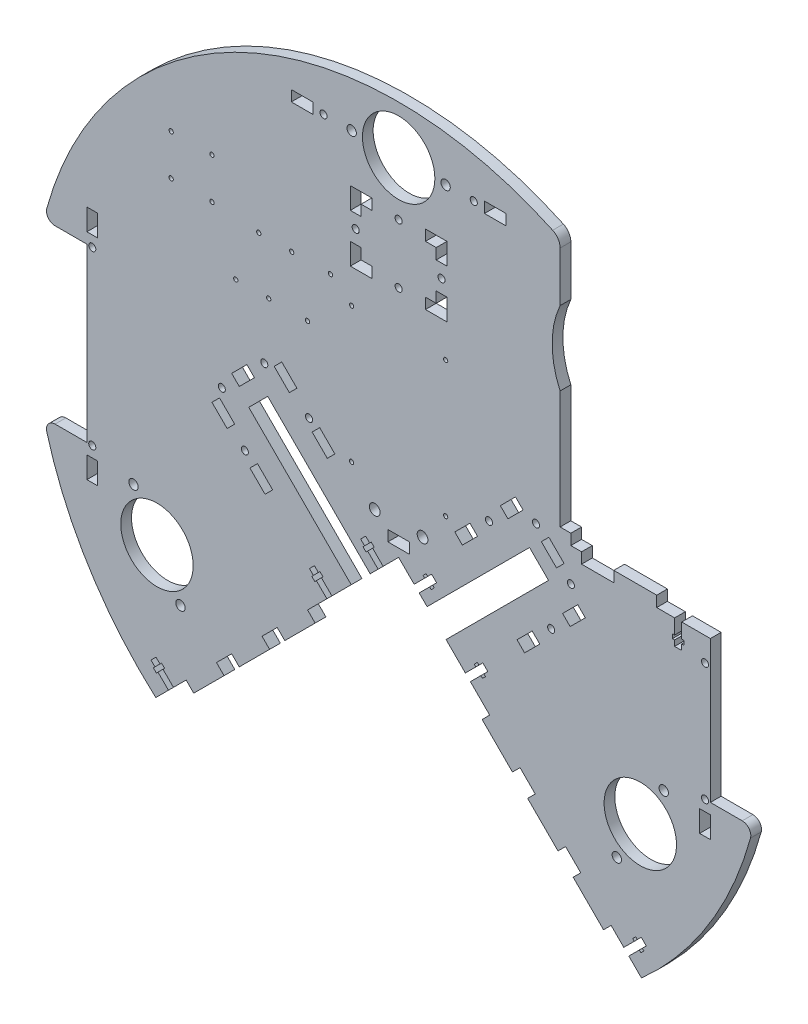
SolidWorks part; units mm, degrees
ref_plane "Front Plane" through (0, 0, 0) normal (0, 0, 1) x (1, 0, 0)
ref_plane "Top Plane" through (0, 0, 0) normal (0, 1, 0) x (1, 0, 0)
ref_plane "Right Plane" through (0, 0, 0) normal (1, 0, 0) x (0, 0, -1)
sketch "Sketch1" plane through (0, 0, 0) normal (0, 0, 1) x (1, 0, 0)
  circle A0 centre (0, 0) radius 215.9
  dimension "D1" = 431.8
extrude "Base Plate Extrusion" add sketch "Sketch1" along normal blind 6.35
sketch "Sketch2" plane through (0, 0, 6.35) normal (0, 0, 1) x (1, 0, 0)
  line L0 (0, 0) -> (0, -230.9791) construction
  line L1 (0, -17.4608) -> (143.6841, -161.1449)
  line L2 (0, -17.4608) -> (-143.6841, -161.1449)
  circle A1 centre (0, 0) radius 215.9 construction
  arc A2 (143.6841, -161.1449) -> (-143.6841, -161.1449) centre (0, 0) cw
  dimension "D1" = 90
  dimension "D2" = 203.2
extrude "V Funnel Cut" cut sketch "Sketch2" against normal through all
sketch "Sketch3" plane through (0, 0, 6.35) normal (0, 0, 1) x (1, 0, 0)
  line L0 (0, 0) -> (251.7982, 0) construction
  line L1 (209.8384, 50.8) -> (184.4384, 50.8)
  line L2 (209.8384, 50.8) -> (209.8384, -50.8)
  line L3 (209.8384, -50.8) -> (184.4384, -50.8)
  line L4 (184.4384, 50.8) -> (184.4384, -50.8)
  arc A0 (143.6841, -161.1449) -> (-143.6841, -161.1449) centre (0, 0) ccw construction
  arc A1 (209.8384, 50.8) -> (209.8384, -50.8) centre (0, 0) cw
  arc M7 (143.6841, -161.1449) -> (-143.6841, -161.1449) centre (0, 0) ccw
  dimension "D1" = 25.4
  dimension "D2" = 101.6
extrude "Wheel Track Cut" cut sketch "Sketch3" against normal through all contours L2 L0 A1 | L4 L0 L2 L1 | L0 L4 L3 L2 | L0 L2 M7 region at (197.1384, 25.4, 6.35) region at (197.1384, -25.4, 6.35) region at (212.266, 19.0862, 6.35) region at (212.266, -19.0862, 6.35)
mirror "Wheel Track Cut Mirror" about plane through (0, 0, 0) normal (1, 0, 0) of "Wheel Track Cut"
sketch "Sketch4" plane through (0, 0, 6.35) normal (0, 0, 1) x (1, 0, 0)
  line L0 (88.68, 15.0926) -> (77.4547, 26.3179)
  line L1 (88.68, 15.0926) -> (28.0633, -45.5241)
  line L2 (77.4547, 26.3179) -> (16.838, -34.2988)
  line L3 (28.0633, -45.5241) -> (16.838, -34.2988)
  line L4 (84.3174, 21.9553) -> (56.956, -5.4061) construction
  line L5 (65.1069, -1.7454) -> (69.5826, 2.7303) construction
  line L6 (65.0924, 7.2204) -> (60.6167, 2.7447) construction
  line L7 (143.6841, -161.1449) -> (0, -17.4608) construction
  dimension "D1" = 15.875
  dimension "D2" = 85.725
extrude "Silo Picker Clearance" cut sketch "Sketch4" against normal through all
sketch "Sketch5" plane through (0, 0, 6.35) normal (0, 0, 1) x (1, 0, 0)
  line L0 (-4.4901, -21.951) -> (0, -17.4608)
  line L1 (-4.4901, -21.951) -> (0, -26.4411)
  line L2 (0, -17.4608) -> (4.4901, -21.951)
  line L3 (0, -26.4411) -> (4.4901, -21.951)
  line L4 (0, -17.4608) -> (-143.6841, -161.1449) construction
  line L6 (4.4901, -21.951) -> (0, -26.4411) construction
  dimension "D1" = 6.35
extrude "V Funnel Corner" add sketch "Sketch5" against normal up to surface (6.35 mm away) up to face at (14.0691, -14.8765, 0)
mirror "Dump Picker Clearance" about plane through (0, 0, 0) normal (1, 0, 0) of "Silo Picker Clearance"
sketch "Sketch6" plane through (8.7304, -8.7304, 0) normal (0.7071, -0.7071, 0) x (0, 0, -1)
  line L0 (-6.35, -52.0342) -> (-6.35, -215.5467) construction
  line L1 (-6.35, -190.1467) -> (0, -190.1467)
  line L2 (-6.35, -190.1467) -> (-6.35, -164.7467)
  line L3 (-6.35, -164.7467) -> (0, -164.7467)
  line L4 (0, -190.1467) -> (0, -164.7467)
  line L5 (0, -52.0342) -> (0, -215.5467) construction
  dimension "D1" = 25.4
  dimension "D2" = 25.4
extrude "V Funnel Tab Left" add sketch "Sketch6" along normal blind 6.35
pattern_linear "V Funnel Tab Pattern Left" count 3 spacing 38.1 along (0.7071, 0.7071, 0) of "V Funnel Tab Left"
sketch "Sketch7" plane through (-8.7304, -8.7304, 0) normal (-0.7071, -0.7071, 0) x (0, 0, 1)
  line L0 (6.35, -215.5467) -> (6.35, -52.0342) construction
  line L1 (6.35, -164.7467) -> (0, -164.7467)
  line L2 (6.35, -164.7467) -> (6.35, -190.1467)
  line L3 (6.35, -190.1467) -> (0, -190.1467)
  line L4 (0, -164.7467) -> (0, -190.1467)
  line L5 (0, -215.5467) -> (0, -52.0342) construction
  dimension "D1" = 25.4
  dimension "D2" = 25.4
extrude "V Funnel Tab Right" add sketch "Sketch7" along normal blind 6.35
pattern_linear "V Funnel Tab Pattern Right" count 3 spacing 38.1 along (-0.7071, 0.7071, 0) of "V Funnel Tab Right"
sketch "Sketch8" plane through (0, 0, 0) normal (0, 0, -1) x (-1, 0, 0)
  line L0 (-70.046, -24.645) -> (-79.0263, -15.6648)
  line L1 (-79.0263, -15.6648) -> (-83.5164, -20.1549)
  line L2 (-83.5164, -20.1549) -> (-74.5361, -29.1352)
  line L3 (-74.5361, -29.1352) -> (-70.046, -24.645)
  line L4 (-96.9868, 2.2957) -> (-101.4769, -2.1944)
  line L5 (-101.4769, -2.1944) -> (-110.4572, 6.7859)
  line L6 (-110.4572, 6.7859) -> (-105.967, 11.276)
  line L7 (-105.967, 11.276) -> (-96.9868, 2.2957)
  line L8 (-97.8965, 28.3267) -> (-88.9163, 37.307)
  line L9 (-88.9163, 37.307) -> (-84.4262, 32.8169)
  line L10 (-84.4262, 32.8169) -> (-93.4064, 23.8366)
  line L11 (-93.4064, 23.8366) -> (-97.8965, 28.3267)
  line L12 (-64.6578, 34.6246) -> (-60.1677, 39.1148)
  line L13 (-60.1677, 39.1148) -> (-69.148, 48.095)
  line L14 (-69.148, 48.095) -> (-73.6381, 43.6049)
  line L15 (-73.6381, 43.6049) -> (-64.6578, 34.6246)
  line L16 (-46.6973, 16.6641) -> (-42.2072, 21.1543)
  line L17 (-42.2072, 21.1543) -> (-33.2269, 12.174)
  line L18 (-33.2269, 12.174) -> (-37.7171, 7.6839)
  line L19 (-37.7171, 7.6839) -> (-46.6973, 16.6641)
  line L20 (-105.967, 11.276) -> (-110.4572, 6.7859) construction
  line L21 (-69.148, 48.095) -> (-73.6381, 43.6049) construction
extrude "Silo Arm Tab Holes" cut sketch "Sketch8" against normal blind 6.35
sketch "Sketch10" plane through (0, 0, 0) normal (0, 0, -1) x (-1, 0, 0)
  line L0 (51.1875, 21.1543) -> (42.2072, 12.174)
  line L1 (42.2072, 12.174) -> (37.7171, 16.6641)
  line L2 (37.7171, 16.6641) -> (46.6973, 25.6444)
  line L3 (46.6973, 25.6444) -> (51.1875, 21.1543)
  line L4 (64.6578, 34.6246) -> (60.1677, 39.1148)
  line L5 (60.1677, 39.1148) -> (69.148, 48.095)
  line L6 (69.148, 48.095) -> (73.6381, 43.6049)
  line L7 (73.6381, 43.6049) -> (64.6578, 34.6246)
  line L8 (89.8026, 36.4207) -> (85.3124, 31.9306)
  line L9 (85.3124, 31.9306) -> (94.2927, 22.9503)
  line L10 (94.2927, 22.9503) -> (98.7828, 27.4404)
  line L11 (98.7828, 27.4404) -> (89.8026, 36.4207)
  line L12 (105.967, 11.276) -> (96.9868, 2.2957)
  line L13 (96.9868, 2.2957) -> (101.4769, -2.1944)
  line L14 (101.4769, -2.1944) -> (110.4572, 6.7859)
  line L15 (110.4572, 6.7859) -> (105.967, 11.276)
  line L16 (88.0065, -15.6648) -> (83.5164, -11.1747)
  line L17 (83.5164, -11.1747) -> (74.5361, -20.1549)
  line L18 (74.5361, -20.1549) -> (79.0263, -24.645)
  line L19 (79.0263, -24.645) -> (88.0065, -15.6648)
  line L20 (37.7171, 16.6641) -> (42.2072, 12.174) construction
  line L21 (74.5361, -20.1549) -> (79.0263, -24.645) construction
extrude "Dump Arm Tab Holes" cut sketch "Sketch10" against normal blind 6.35
sketch "Sketch11" plane through (0, 0, 0) normal (0, 0, -1) x (-1, 0, 0)
  line L1 (184.4384, -69.85) -> (178.0884, -69.85)
  line L2 (184.4384, -69.85) -> (184.4384, -57.15)
  line L3 (184.4384, -57.15) -> (178.0884, -57.15)
  line L4 (178.0884, -69.85) -> (178.0884, -57.15)
  line L5 (184.4384, 57.15) -> (178.0884, 57.15)
  line L6 (184.4384, 57.15) -> (184.4384, 69.85)
  line L7 (184.4384, 69.85) -> (178.0884, 69.85)
  line L8 (178.0884, 57.15) -> (178.0884, 69.85)
  line L9 (-178.0884, -69.85) -> (-184.4384, -69.85)
  line L10 (-178.0884, -69.85) -> (-178.0884, -57.15)
  line L11 (-178.0884, -57.15) -> (-184.4384, -57.15)
  line L12 (-184.4384, -69.85) -> (-184.4384, -57.15)
  line L13 (-178.0884, 57.15) -> (-184.4384, 57.15)
  line L14 (-178.0884, 57.15) -> (-178.0884, 69.85)
  line L15 (-178.0884, 69.85) -> (-184.4384, 69.85)
  line L16 (-184.4384, 57.15) -> (-184.4384, 69.85)
extrude "Wheel Support Tab Holes" cut sketch "Sketch11" against normal blind 6.35
sketch "Sketch13" plane through (0, 0, 6.35) normal (0, 0, 1) x (1, 0, 0)
  circle A0 centre (0, 187.325) radius 21.4313
  circle A1 centre (27.7812, 187.325) radius 2.7781
  circle A2 centre (-27.7813, 187.325) radius 2.7781
  dimension "D1" = 42.8625
  dimension "D2" = 5.5562
extrude "Caster Wheel Hole" cut sketch "Sketch13" against normal through all
sketch "Sketch14" plane through (0, 0, 6.35) normal (0, 0, 1) x (1, 0, 0)
  line L0 (184.4384, 48.6664) -> (178.0884, 52.9336) construction
  line L1 (184.4384, 50.8) -> (184.4384, -50.8) construction
  line L2 (178.0884, 48.6664) -> (184.4384, 48.6664) construction
  line L3 (184.4384, 52.9336) -> (178.0884, 48.6664) construction
  line L4 (184.4384, -52.9336) -> (178.0884, -48.6664) construction
  line L5 (184.4384, -48.6664) -> (178.0884, -52.9336) construction
  line L6 (178.0884, -48.6664) -> (184.4384, -48.6664) construction
  circle A0 centre (181.2634, 50.8) radius 2.0955
  circle A1 centre (181.2634, -50.8) radius 2.0955
  dimension "D1" = 4.191
extrude "Wheel Support Hole" cut sketch "Sketch14" against normal through all
mirror "Wheel Support Hole Mirror" about plane through (0, 0, 0) normal (1, 0, 0) of "Wheel Support Hole"
sketch "Sketch15" plane through (0, 0, 6.35) normal (0, 0, 1) x (1, 0, 0)
  line L0 (-134.7038, -152.1647) -> (-152.6084, -134.2601) construction
  line L1 (-125.7236, -143.1844) -> (-143.6841, -161.1449) construction
  line L2 (-40.9724, -58.4333) -> (-60.7132, -38.6924) construction
  line L3 (-28.0633, -45.5241) -> (-53.8815, -71.3424) construction
  line L4 (-10.6641, -28.1249) -> (-27.2834, -11.5055) construction
  line L5 (-4.4901, -21.951) -> (-16.838, -34.2988) construction
  line B0 (-136.1856, -153.6464) -> (-133.2221, -150.6829)
  line B1 (-141.2145, -142.6905) -> (-140.2716, -141.7476)
  line B2 (-140.2716, -141.7476) -> (-138.4755, -143.5436)
  line B3 (-138.4755, -143.5436) -> (-139.4185, -144.4866)
  line B4 (-139.4185, -144.4866) -> (-133.2221, -150.6829)
  line B5 (-141.2145, -142.6905) -> (-143.5494, -140.3556)
  line B6 (-143.5494, -140.3556) -> (-146.5129, -143.3191)
  line B7 (-144.178, -145.654) -> (-146.5129, -143.3191)
  line B8 (-142.382, -147.45) -> (-136.1856, -153.6464)
  line B9 (-143.3249, -148.393) -> (-142.382, -147.45)
  line B10 (-145.1209, -146.5969) -> (-143.3249, -148.393)
  line B11 (-144.178, -145.654) -> (-145.1209, -146.5969)
  line B12 (-42.4542, -59.915) -> (-39.4907, -56.9515)
  line B13 (-47.4831, -48.9591) -> (-46.5402, -48.0162)
  line B14 (-46.5402, -48.0162) -> (-44.7441, -49.8122)
  line B15 (-44.7441, -49.8122) -> (-45.6871, -50.7551)
  line B16 (-45.6871, -50.7551) -> (-39.4907, -56.9515)
  line B17 (-47.4831, -48.9591) -> (-49.818, -46.6242)
  line B18 (-49.818, -46.6242) -> (-52.7815, -49.5877)
  line B19 (-50.4466, -51.9226) -> (-52.7815, -49.5877)
  line B20 (-48.6505, -53.7186) -> (-42.4542, -59.915)
  line B21 (-49.5935, -54.6615) -> (-48.6505, -53.7186)
  line B22 (-51.3895, -52.8655) -> (-49.5935, -54.6615)
  line B23 (-50.4466, -51.9226) -> (-51.3895, -52.8655)
  line B24 (-12.1458, -29.6066) -> (-9.1823, -26.6431)
  line B25 (-17.1747, -18.6507) -> (-16.2318, -17.7078)
  line B26 (-16.2318, -17.7078) -> (-14.4358, -19.5038)
  line B27 (-14.4358, -19.5038) -> (-15.3787, -20.4468)
  line B28 (-15.3787, -20.4468) -> (-9.1823, -26.6431)
  line B29 (-17.1747, -18.6507) -> (-19.5096, -16.3159)
  line B30 (-19.5096, -16.3159) -> (-22.4731, -19.2793)
  line B31 (-20.1382, -21.6142) -> (-22.4731, -19.2793)
  line B32 (-18.3422, -23.4103) -> (-12.1458, -29.6066)
  line B33 (-19.2851, -24.3532) -> (-18.3422, -23.4103)
  line B34 (-21.0812, -22.5571) -> (-19.2851, -24.3532)
  line B35 (-20.1382, -21.6142) -> (-21.0812, -22.5571)
sketch_block_instance "TSlot-1"
sketch_block "TSlot" parameters "D1"=3.302, "D2"=2.54, "D3"=3.175, "D4"=8.763, "D5"=1.3462
sketch_block_instance "TSlot-3"
sketch_block_instance "TSlot-4"
extrude "V Funnel T Slot Cut Out" cut sketch "Sketch15" against normal through all
mirror "V Funnel T Slot Cut Out Mirror" about plane through (0, 0, 0) normal (1, 0, 0) of "V Funnel T Slot Cut Out"
sketch "Sketch19" plane through (0, 0, 6.35) normal (0, 0, 1) x (1, 0, 0)
  line L0 (46.5836, 190.5) -> (42.3164, 184.15) construction
  line L1 (46.5836, 184.15) -> (42.3164, 190.5) construction
  line L2 (-42.3164, 190.5) -> (-46.5836, 184.15) construction
  line L3 (-42.3164, 184.15) -> (-46.5836, 190.5) construction
  circle A0 centre (44.45, 187.325) radius 2.0955
  circle A1 centre (-44.45, 187.325) radius 2.0955
  dimension "D1" = 4.191
extrude "Switch Plate Holes" cut sketch "Sketch19" against normal through all
sketch "Sketch20" plane through (0, 0, 0) normal (0, 0, -1) x (-1, 0, 0)
  line L1 (-50.8, 184.15) -> (-63.5, 184.15)
  line L2 (-50.8, 184.15) -> (-50.8, 190.5)
  line L3 (-50.8, 190.5) -> (-63.5, 190.5)
  line L4 (-63.5, 184.15) -> (-63.5, 190.5)
  line L5 (63.5, 184.15) -> (50.8, 184.15)
  line L6 (63.5, 184.15) -> (63.5, 190.5)
  line L7 (63.5, 190.5) -> (50.8, 190.5)
  line L8 (50.8, 184.15) -> (50.8, 190.5)
extrude "Swith Plate Tab Holes" cut sketch "Sketch20" against normal through all
sketch "Sketch26" plane through (0, 0, 6.35) normal (0, 0, 1) x (1, 0, 0)
  line L0 (89.5152, -5.1758) -> (90.988, -12.6833) construction
  line L1 (86.4978, -8.1932) -> (94.0053, -9.666) construction
  line L2 (52.6961, 31.6432) -> (54.1689, 24.1357) construction
  line L3 (49.6788, 28.6258) -> (57.1863, 27.1531) construction
  line L4 (105.6855, 20.5377) -> (98.178, 19.065) construction
  line L5 (102.6682, 23.5551) -> (101.1954, 16.0476) construction
  line L6 (82.0136, 44.2097) -> (80.5408, 36.7022) construction
  line L7 (85.0309, 41.1923) -> (77.5234, 39.7196) construction
  circle A0 centre (90.2516, -8.9296) radius 2.0955
  circle A1 centre (53.4325, 27.8895) radius 2.0955
  circle A2 centre (101.9318, 19.8014) radius 2.0955
  circle A3 centre (81.2772, 40.4559) radius 2.0955
  dimension "D1" = 4.191
extrude "Silo Arm Holes" cut sketch "Sketch26" against normal through all
sketch "Sketch27" plane through (0, 0, 6.35) normal (0, 0, 1) x (1, 0, 0)
  line L0 (-49.2298, 28.1768) -> (-56.7373, 26.7041) construction
  line L1 (-52.2471, 31.1942) -> (-53.7199, 23.6867) construction
  line L2 (-80.2116, 46.0116) -> (-78.7389, 38.5041) construction
  line L3 (-83.229, 42.9942) -> (-75.7215, 41.5215) construction
  line L4 (-105.3564, 20.8669) -> (-103.8836, 13.3594) construction
  line L5 (-108.3737, 17.8495) -> (-100.8662, 16.3768) construction
  line L6 (-94.6968, -8.9745) -> (-87.2432, -7.4479) construction
  line L7 (-91.7333, -11.938) -> (-90.2067, -4.4844) construction
  circle A0 centre (-52.9835, 27.4404) radius 2.0955
  circle A1 centre (-79.4753, 42.2579) radius 2.0955
  circle A2 centre (-104.62, 17.1131) radius 2.0955
  circle A3 centre (-90.97, -8.2112) radius 2.0955
  dimension "D1" = 4.191
extrude "Dump Arm Holes" cut sketch "Sketch27" against normal through all
fillet "Wheel Slot Fillet" radius 5.08 4 edges at (209.8384, -50.8, 3.175) (209.8384, 50.8, 3.175) (-209.8384, -50.8, 3.175) (-209.8384, 50.8, 3.175)
sketch "Sketch28" plane through (0, 0, 6.35) normal (0, 0, 1) x (1, 0, 0)
  line L0 (0, 0) -> (0, 258.9974) construction
  line L1 (0, 0) -> (249.4479, -144.0188) construction
  line L2 (0, 0) -> (-249.719, -144.1753) construction
  line L3 (-142.9808, -82.55) -> (-156.8714, -58.4907) construction
  line L4 (-27.7813, 187.325) -> (0, 187.325) construction
  line L5 (-142.9808, -82.55) -> (-129.0902, -106.6093) construction
  circle A0 centre (-142.9808, -82.55) radius 21.4313
  circle A1 centre (0, 187.325) radius 21.4313 construction
  circle A2 centre (-156.8714, -58.4907) radius 2.7781
  circle A3 centre (-27.7813, 187.325) radius 2.7781 construction
  circle A4 centre (-129.0902, -106.6093) radius 2.7781
  dimension "D1" = 120
  dimension "D2" = 120
  dimension "D3" = 165.1
extrude "Front Caster Holes" cut sketch "Sketch28" against normal through all
mirror "Front Caster Hole Mirror" about plane through (0, 0, 0) normal (1, 0, 0) of "Front Caster Holes"
sketch "Gyro Holes" plane through (0, 0, 6.35) normal (0, 0, 1) x (1, 0, 0)
  line L1 (-134.5682, 109.4626) -> (-110.4382, 109.4626) construction
  line L2 (-134.5682, 109.4626) -> (-134.5682, 133.5926) construction
  line L3 (-134.5682, 133.5926) -> (-110.4382, 133.5926) construction
  line L4 (-110.4382, 109.4626) -> (-110.4382, 133.5926) construction
  line L5 (-134.5682, 109.4626) -> (-110.4382, 133.5926) construction
  line L6 (-134.5682, 133.5926) -> (-110.4382, 109.4626) construction
  circle A0 centre (-134.5682, 133.5926) radius 1.27
  circle A1 centre (-110.4382, 133.5926) radius 1.27
  circle A2 centre (-110.4382, 109.4626) radius 1.27
  circle A3 centre (-134.5682, 109.4626) radius 1.27
  point P0 (-122.5032, 121.5276)
  dimension "D2" = 24.13
  dimension "D1" = 2.54
extrude "GyroHoles" cut sketch "Gyro Holes" against normal through all
sketch "MotorControllerHoleSketch" plane through (0, 0, 6.35) normal (0, 0, 1) x (1, 0, 0)
  line L0 (0, 215.9) -> (0, -26.4411) construction
  line L2 (-27.82, 17.5746) -> (27.82, 17.5746) construction
  line L3 (-27.82, 17.5746) -> (-27.82, 97.6146) construction
  line L4 (-27.82, 97.6146) -> (27.82, 97.6146) construction
  line L5 (27.82, 17.5746) -> (27.82, 97.6146) construction
  line L6 (-27.82, 17.5746) -> (27.82, 97.6146) construction
  line L7 (-27.82, 97.6146) -> (27.82, 17.5746) construction
  arc A0 (208.1777, 57.2265) -> (-208.1777, 57.2265) centre (0, 0) ccw construction
  circle A1 centre (-27.82, 97.6146) radius 1.25
  circle A2 centre (27.82, 97.6146) radius 1.25
  circle A3 centre (27.82, 17.5746) radius 1.25
  circle A4 centre (-27.82, 17.5746) radius 1.25
  point P6 (0, 57.5946)
  dimension "D1" = 2.5
  dimension "D2" = 55.64
  dimension "D3" = 80.04
extrude "Motor Controller Hole" cut sketch "MotorControllerHoleSketch" against normal through all
sketch "Sketch31" plane through (0, 0, 6.35) normal (0, 0, 1) x (1, 0, 0)
  line L0 (-58.5988, 118.6025) -> (-58.5988, 61.2016) construction
  line L1 (-40.3087, 76.7541) -> (-53.9191, 76.7541) construction
  line L2 (-40.3087, 76.7541) -> (-40.3087, 107.5065) construction
  line L3 (-40.3087, 107.5065) -> (-53.9191, 107.5065) construction
  line L4 (-53.9191, 76.7541) -> (-53.9191, 107.5065) construction
  line L5 (-40.3087, 76.7541) -> (-53.9191, 107.5065) construction
  line L6 (-40.3087, 107.5065) -> (-53.9191, 76.7541) construction
  line L7 (-63.2785, 76.7541) -> (-76.8888, 76.7541) construction
  line L8 (-63.2785, 76.7541) -> (-63.2785, 107.5065) construction
  line L9 (-63.2785, 107.5065) -> (-76.8888, 107.5065) construction
  line L10 (-76.8888, 76.7541) -> (-76.8888, 107.5065) construction
  line L11 (-63.2785, 76.7541) -> (-76.8888, 107.5065) construction
  line L12 (-63.2785, 107.5065) -> (-76.8888, 76.7541) construction
  line L13 (-70.0836, 92.1303) -> (-47.1139, 92.1303) construction
  line L15 (-82.7354, 76.7541) -> (-96.3457, 76.7541) construction
  line L16 (-82.7354, 76.7541) -> (-82.7354, 107.5065) construction
  line L17 (-82.7354, 107.5065) -> (-96.3457, 107.5065) construction
  line L18 (-96.3457, 76.7541) -> (-96.3457, 107.5065) construction
  line L19 (-82.7354, 76.7541) -> (-96.3457, 107.5065) construction
  line L20 (-82.7354, 107.5065) -> (-96.3457, 76.7541) construction
  circle A0 centre (-76.8888, 76.7541) radius 1.27
  circle A1 centre (-63.2785, 107.5065) radius 1.27
  circle A2 centre (-53.9191, 76.7541) radius 1.27
  circle A3 centre (-40.3087, 107.5065) radius 1.27
  circle A4 centre (-82.7354, 107.5065) radius 1.27
  circle A5 centre (-96.3457, 76.7541) radius 1.27
  point P0 (-47.1139, 92.1303)
  point P5 (-70.0836, 92.1303)
  point P18 (-89.5406, 92.1303)
  dimension "D1" = 2.54
  dimension "D2" = 33.6296
extrude "BuckConverterHoles" cut sketch "Sketch31" against normal through all
sketch "Sketch34" plane through (0, 0, 0) normal (0, 0, -1) x (-1, 0, 0)
  line L1 (-28.575, 158.75) -> (-15.875, 158.75)
  line L2 (-28.575, 158.75) -> (-28.575, 152.4)
  line L3 (-22.225, 152.4) -> (-15.875, 152.4)
  line L4 (-15.875, 158.75) -> (-15.875, 152.4)
  line L5 (15.875, 158.75) -> (28.575, 158.75)
  line L6 (15.875, 158.75) -> (15.875, 152.4)
  line L7 (15.875, 152.4) -> (22.225, 152.4)
  line L8 (28.575, 158.75) -> (28.575, 152.4)
  line L9 (15.875, 123.825) -> (22.225, 123.825)
  line L10 (15.875, 123.825) -> (15.875, 117.475)
  line L11 (15.875, 117.475) -> (28.575, 117.475)
  line L12 (28.575, 123.825) -> (28.575, 117.475)
  line L13 (-22.225, 123.825) -> (-15.875, 123.825)
  line L14 (-28.575, 123.825) -> (-28.575, 117.475)
  line L15 (-28.575, 117.475) -> (-15.875, 117.475)
  line L16 (-15.875, 123.825) -> (-15.875, 117.475)
  line L17 (-28.575, 130.175) -> (-22.225, 130.175)
  line L18 (-28.575, 130.175) -> (-28.575, 123.825)
  line L20 (-22.225, 130.175) -> (-22.225, 123.825)
  line L22 (-28.575, 152.4) -> (-28.575, 146.05)
  line L23 (-28.575, 146.05) -> (-22.225, 146.05)
  line L24 (-22.225, 152.4) -> (-22.225, 146.05)
  line L26 (22.225, 152.4) -> (22.225, 146.05)
  line L27 (22.225, 146.05) -> (28.575, 146.05)
  line L28 (28.575, 152.4) -> (28.575, 146.05)
  line L29 (22.225, 130.175) -> (28.575, 130.175)
  line L30 (22.225, 130.175) -> (22.225, 123.825)
  line L32 (28.575, 130.175) -> (28.575, 123.825)
extrude "Cut-Extrude6" cut sketch "Sketch34" against normal through all
sketch "Sketch35" plane through (0, 0, 6.35) normal (0, 0, 1) x (1, 0, 0)
  line L0 (-22.225, 136.017) -> (-28.575, 140.208) construction
  line L1 (-28.575, 136.017) -> (-22.225, 140.208) construction
  line L2 (-2.0955, 152.4) -> (2.0955, 158.75) construction
  line L3 (2.0955, 152.4) -> (-2.0955, 158.75) construction
  line L4 (22.225, 136.017) -> (28.575, 140.208) construction
  line L5 (22.225, 140.208) -> (28.575, 136.017) construction
  line L6 (2.0955, 123.825) -> (-2.0955, 117.475) construction
  line L7 (-2.0955, 123.825) -> (2.0955, 117.475) construction
  circle A0 centre (0, 120.65) radius 2.0955
  circle A1 centre (25.4, 138.1125) radius 2.0955
  circle A2 centre (0, 155.575) radius 2.0955
  circle A3 centre (-25.4, 138.1125) radius 2.0955
  dimension "D1" = 4.191
extrude "Cut-Extrude7" cut sketch "Sketch35" against normal through all
sketch "Sketch37" [suppressed] plane through (0, 0, 0) normal (0, 0, -1) x (-1, 0, 0)
  line L0 (-86.0134, 49.1901) -> (-174.9134, 49.1901) construction
  line L1 (-117.7634, 49.1901) -> (-143.1634, 49.1901)
  line L2 (-117.7634, 49.1901) -> (-117.7634, 55.5401)
  line L3 (-117.7634, 55.5401) -> (-143.1634, 55.5401)
  line L4 (-143.1634, 49.1901) -> (-143.1634, 55.5401)
  line L5 (-117.7634, 49.1901) -> (-117.7634, 55.5401) construction
sketch "Sketch41" plane through (0, 0, 6.35) normal (0, 0, 1) x (1, 0, 0)
  line L0 (95.5384, 193.611) -> (95.5384, 45.8763)
  line L1 (95.5384, 49.1901) -> (95.5384, 45.8763) construction
  line L2 (95.5384, 45.8763) -> (101.8884, 45.8763)
  line L3 (101.8884, 45.8763) -> (101.8884, 39.5263)
  line L4 (101.8884, 39.5263) -> (108.2384, 39.5263)
  line L5 (108.2384, 39.5263) -> (108.2384, 33.1763)
  line L6 (108.2384, 33.1763) -> (218.8605, 33.1763)
  line L7 (218.8605, 33.1763) -> (218.8605, 193.611)
  line L8 (218.8605, 193.611) -> (95.5384, 193.611)
  arc A0 (208.1777, 57.2265) -> (-208.1777, 57.2265) centre (0, 0) ccw construction
extrude "Cut-Extrude13" cut sketch "Sketch41" against normal through all
fillet "Fillet1" radius 7.62 1 edges at (95.5384, 193.611, 3.175)
sketch "Sketch42" plane through (0, 0, 6.35) normal (0, 0, 1) x (1, 0, 0)
  line L0 (95.5384, 159.3081) -> (95.5384, 115.5739)
  line L1 (95.5384, 188.8145) -> (95.5384, 45.8763) construction
  arc A1 (95.5384, 115.5739) -> (95.5384, 159.3081) centre (143.7787, 137.441) cw
extrude "Cut-Extrude14" cut sketch "Sketch42" against normal through all
sketch "Sketch44" plane through (0, 33.1763, 0) normal (0, 1, 0) x (1, 0, 0)
  line L0 (108.2384, -6.35) -> (184.4384, -6.35) construction
  line L1 (127.2884, -6.35) -> (152.6884, -6.35)
  line L2 (127.2884, -6.35) -> (127.2884, 0)
  line L3 (127.2884, 0) -> (152.6884, 0)
  line L4 (152.6884, -6.35) -> (152.6884, 0)
  line L5 (108.2384, 0) -> (184.4384, 0) construction
extrude "Boss-Extrude2" add sketch "Sketch44" along normal blind 6.35
sketch "Sketch45" plane through (0, 0, 6.35) normal (0, 0, 1) x (1, 0, 0)
  line L0 (152.6884, 33.1763) -> (184.4384, 33.1763) construction
  line L1 (163.2929, 39.5263) -> (163.2929, 33.1763) construction
  line B0 (167.4839, 33.1763) -> (163.2929, 33.1763)
  line B1 (163.2929, 21.8733) -> (161.9594, 21.8733)
  line B2 (161.9594, 21.8733) -> (161.9594, 24.4133)
  line B3 (161.9594, 24.4133) -> (163.2929, 24.4133)
  line B4 (163.2929, 24.4133) -> (163.2929, 33.1763)
  line B5 (163.2929, 21.8733) -> (163.2929, 18.5713)
  line B6 (163.2929, 18.5713) -> (167.4839, 18.5713)
  line B7 (167.4839, 21.8733) -> (167.4839, 18.5713)
  line B8 (167.4839, 24.4133) -> (167.4839, 33.1763)
  line B9 (168.8174, 24.4133) -> (167.4839, 24.4133)
  line B10 (168.8174, 21.8733) -> (168.8174, 24.4133)
  line B11 (167.4839, 21.8733) -> (168.8174, 21.8733)
  line B12 (165.3884, 33.1763) -> (165.3884, 18.5713) construction
  line B13 (161.9594, 23.1433) -> (172.0532, 23.1433) construction
sketch_block_instance "TSlot-7"
extrude "Cut-Extrude15" cut sketch "Sketch45" against normal through all
sketch "Sketch47" plane through (0, 0, 0) normal (0, 0, -1) x (-1, 0, 0)
  line L1 (-6.35, -12.6983) -> (6.35, -12.6983)
  line L2 (-6.35, -12.6983) -> (-6.35, -6.3483)
  line L3 (-6.35, -6.3483) -> (6.35, -6.3483)
  line L4 (6.35, -12.6983) -> (6.35, -6.3483)
extrude "Cut-Extrude16" cut sketch "Sketch47" against normal through all
extrude "Boss-Extrude1" [suppressed] add sketch "Sketch37" against normal up to surface (6.35 mm away)
sketch "Sketch38" plane through (0, 0, 0) normal (0, 0, -1) x (-1, 0, 0)
  line L2 (-186.392, 104.3946) -> (-275.292, 104.3946) construction
  line L4 (-143.1634, 55.5401) -> (-143.1634, 49.1901) construction
  line L5 (-268.942, 186.9446) -> (-268.942, 110.7446) construction
  line L7 (-192.742, 110.7446) -> (-192.742, 186.9446) construction
  line L8 (-117.7634, 49.1901) -> (-117.7634, 55.5401) construction
  line B0 (-153.1572, 104.3946) -> (-157.3482, 104.3946)
  line B1 (-157.3482, 93.0916) -> (-158.6817, 93.0916)
  line B2 (-158.6817, 93.0916) -> (-158.6817, 95.6316)
  line B3 (-158.6817, 95.6316) -> (-157.3482, 95.6316)
  line B4 (-157.3482, 95.6316) -> (-157.3482, 104.3946)
  line B5 (-157.3482, 93.0916) -> (-157.3482, 89.7896)
  line B6 (-157.3482, 89.7896) -> (-153.1572, 89.7896)
  line B7 (-153.1572, 93.0916) -> (-153.1572, 89.7896)
  line B8 (-153.1572, 95.6316) -> (-153.1572, 104.3946)
  line B9 (-151.8237, 95.6316) -> (-153.1572, 95.6316)
  line B10 (-151.8237, 93.0916) -> (-151.8237, 95.6316)
  line B11 (-153.1572, 93.0916) -> (-151.8237, 93.0916)
  line B12 (-155.2527, 104.3946) -> (-155.2527, 89.7896) construction
  line B13 (-203.9572, 104.3946) -> (-208.1482, 104.3946)
  line B14 (-208.1482, 93.0916) -> (-209.4817, 93.0916)
  line B15 (-209.4817, 93.0916) -> (-209.4817, 95.6316)
  line B16 (-209.4817, 95.6316) -> (-208.1482, 95.6316)
  line B17 (-208.1482, 95.6316) -> (-208.1482, 104.3946)
  line B18 (-208.1482, 93.0916) -> (-208.1482, 89.7896)
  line B19 (-208.1482, 89.7896) -> (-203.9572, 89.7896)
  line B20 (-203.9572, 93.0916) -> (-203.9572, 89.7896)
  line B21 (-203.9572, 95.6316) -> (-203.9572, 104.3946)
  line B22 (-202.6237, 95.6316) -> (-203.9572, 95.6316)
  line B23 (-202.6237, 93.0916) -> (-202.6237, 95.6316)
  line B24 (-203.9572, 93.0916) -> (-202.6237, 93.0916)
  line B25 (-206.0527, 104.3946) -> (-206.0527, 89.7896) construction
sketch_block_instance "TSlot-5"
sketch_block_instance "TSlot-6"
extrude "Cut-Extrude9" [suppressed] cut sketch "Sketch38" against normal through all
sketch "Sketch39" plane through (0, 0, 0) normal (0, 0, -1) x (-1, 0, 0)
  line L0 (-184.4384, 33.1763) -> (-227.6876, 33.1763)
  line L1 (-95.5384, 33.1763) -> (-184.4384, 33.1763)
  line L2 (-95.5384, 33.1763) -> (-95.5384, 122.0763)
  line L3 (-95.5384, 122.0763) -> (-184.4384, 122.0763)
  arc A0 (-227.6876, 33.1763) -> (-184.4384, 122.0763) centre (-22.9914, -11.4365) cw
extrude "Cut-Extrude11" cut sketch "Sketch39" against normal through all
sketch "Sketch40" plane through (0, 0, 6.35) normal (0, 0, 1) x (1, 0, 0)
  line L0 (178.0884, 21.1455) -> (184.4384, 16.9545) construction
  line L1 (184.4384, 33.1763) -> (184.4384, -50.8) construction
  line L2 (178.0884, 16.9545) -> (184.4384, 16.9545) construction
  line L3 (178.0884, 16.9545) -> (184.4384, 21.1455) construction
  circle A0 centre (181.2634, 19.05) radius 2.0955
  dimension "D1" = 4.191
extrude "Cut-Extrude12" cut sketch "Sketch40" against normal through all
sketch "Sketch48" plane through (0, 33.1763, 0) normal (0, 1, 0) x (1, 0, 0)
  line L0 (95.5384, 0) -> (163.2929, 0) construction
  line L1 (95.5384, -6.35) -> (108.2384, -6.35)
  line L2 (95.5384, -6.35) -> (95.5384, 0)
  line L3 (95.5384, 0) -> (108.2384, 0)
  line L4 (108.2384, -6.35) -> (108.2384, 0)
extrude "Boss-Extrude3" add sketch "Sketch48" along normal blind 6.35
sketch "Sketch49" plane through (95.5384, 0, 0) normal (1, 0, 0) x (0, 0, -1)
  line L0 (0, 115.5739) -> (0, 39.5263) construction
  line L1 (-6.35, 39.5263) -> (0, 39.5263)
  line L2 (-6.35, 39.5263) -> (-6.35, 45.8763)
  line L3 (-6.35, 45.8763) -> (0, 45.8763)
  line L4 (0, 39.5263) -> (0, 45.8763)
  line L5 (0, 45.8763) -> (-6.35, 45.8763) construction
extrude "Boss-Extrude4" add sketch "Sketch49" along normal blind 6.35
sketch "Sketch50" plane through (0, 0, 0) normal (0, 0, -1) x (-1, 0, 0)
  line L0 (0, -17.4608) -> (-4.4901, -21.951)
  line L1 (-4.4901, -21.951) -> (0, -26.4411)
  line L2 (0, -26.4411) -> (4.4901, -21.951)
  line L3 (4.4901, -21.951) -> (0, -17.4608)
extrude "Cut-Extrude17" cut sketch "Sketch50" against normal through all
sketch "Sketch51" plane through (0, 0, 0) normal (0, 0, -1) x (-1, 0, 0)
  line L0 (0, 0) -> (0, 11.938) construction
  circle A0 centre (14.1392, 0) radius 3.175
  circle A1 centre (-14.1392, 0) radius 3.175
  dimension "D1" = 6.35
extrude "Cut-Extrude18" cut sketch "Sketch51" against normal through all
sketch "Sketch52" plane through (0, 33.1763, 0) normal (0, 1, 0) x (1, 0, 0)
  line L0 (108.2384, -6.35) -> (163.2929, -6.35) construction
  line L1 (127.2884, -6.35) -> (152.6884, -6.35)
  line L2 (127.2884, -6.35) -> (127.2884, 0)
  line L3 (127.2884, 0) -> (152.6884, 0)
  line L4 (152.6884, -6.35) -> (152.6884, 0)
  line L5 (127.2884, -6.35) -> (127.2884, 0) construction
  line L6 (108.2384, 0) -> (163.2929, 0) construction
  line L7 (152.6884, -6.35) -> (152.6884, 0) construction
extrude "Boss-Extrude5" add sketch "Sketch52" along normal blind 6.35
